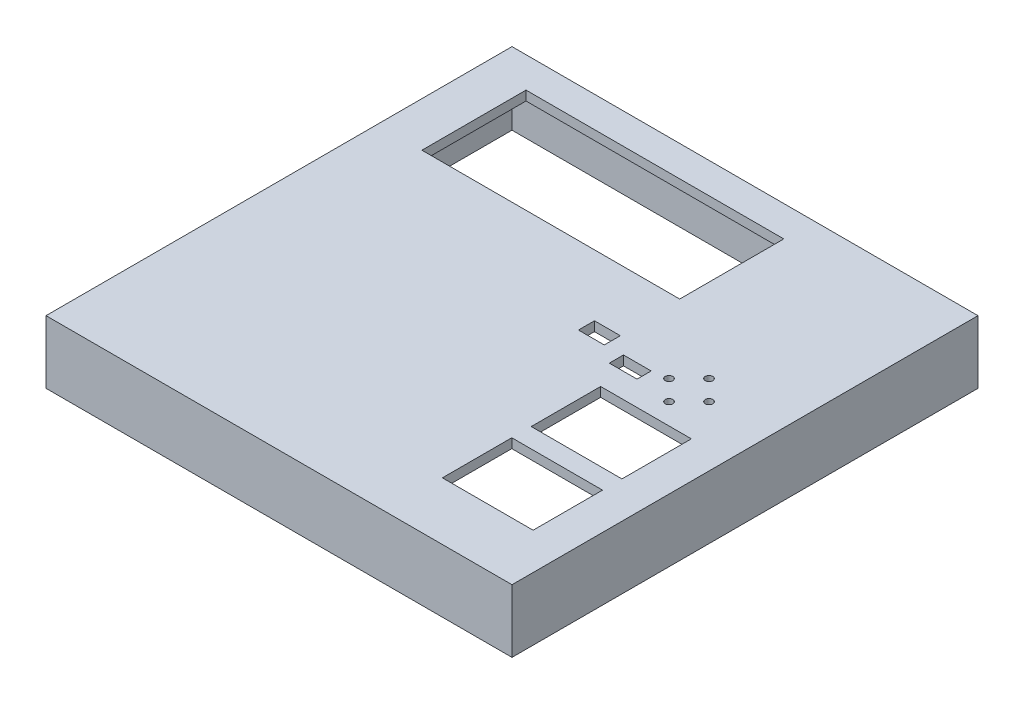
SolidWorks part; units mm, degrees
ref_plane "Front Plane" through (0, 0, 0) normal (0, 0, 1) x (1, 0, 0)
ref_plane "Top Plane" through (0, 0, 0) normal (0, 1, 0) x (1, 0, 0)
ref_plane "Right Plane" through (0, 0, 0) normal (1, 0, 0) x (0, 0, -1)
sketch "Sketch1" plane through (0, 0, 0) normal (0, 1, 0) x (1, 0, 0)
  line L1 (-39.4497, 23.4449) -> (54.5503, 23.4449)
  line L2 (-39.4497, 23.4449) -> (-39.4497, -70.5551)
  line L3 (-39.4497, -70.5551) -> (54.5503, -70.5551)
  line L4 (54.5503, 23.4449) -> (54.5503, -70.5551)
  dimension "D1" = 94
  dimension "D2" = 94
extrude "Boss-Extrude1" add sketch "Sketch1" along normal blind 12.7
sketch "Sketch2" plane through (0, 12.7, 0) normal (0, 1, 0) x (1, 0, 0)
  line L1 (-30.4389, 17.2618) -> (21.5611, 17.2618)
  line L2 (-30.4389, 17.2618) -> (-30.4389, -3.7382)
  line L3 (-30.4389, -3.7382) -> (21.5611, -3.7382)
  line L4 (21.5611, 17.2618) -> (21.5611, -3.7382)
  line L5 (16.7611, -16.1312) -> (21.9778, -16.1312)
  line L6 (-37.6389, 21.9688) -> (52.1611, 21.9688)
  line L7 (-37.6389, 21.9688) -> (-37.6389, -68.4562)
  line L8 (-37.6389, -68.4562) -> (52.1611, -68.4562)
  line L9 (52.1611, 21.9688) -> (52.1611, -68.4562)
  line L10 (28.8611, -26.9865) -> (47.1611, -26.9865)
  line L11 (28.8611, -26.9865) -> (28.8611, -40.9865)
  line L12 (28.8611, -40.9865) -> (47.1611, -40.9865)
  line L13 (47.1611, -26.9865) -> (47.1611, -40.9865)
  line L14 (28.8611, -44.9062) -> (47.1611, -44.9062)
  line L15 (28.8611, -44.9062) -> (28.8611, -58.9062)
  line L16 (28.8611, -58.9062) -> (47.1611, -58.9062)
  line L17 (47.1611, -44.9062) -> (47.1611, -58.9062)
  line L18 (16.7611, -16.1312) -> (16.7611, -19.368)
  line L19 (16.7611, -19.368) -> (21.9778, -19.368)
  line L20 (21.9778, -16.1312) -> (21.9778, -19.368)
  line L21 (25.6611, -19.1792) -> (31.2504, -19.1792)
  line L22 (25.6611, -19.1792) -> (25.6611, -22.0359)
  line L23 (25.6611, -22.0359) -> (31.2504, -22.0359)
  line L24 (31.2504, -19.1792) -> (31.2504, -22.0359)
  circle A0 centre (38.4111, -18.7062) radius 6.05
  circle A7 centre (38.4111, -14.6721) radius 0.762
  circle A8 centre (34.377, -18.7062) radius 0.762
  circle A9 centre (38.4111, -22.7403) radius 0.762
  circle A10 centre (42.4453, -18.7062) radius 0.762
  dimension "D15" = 12.1
  dimension "D18" = 1.524
  dimension "D19" = 1.524
  dimension "D20" = 1.524
  dimension "D21" = 1.524
  dimension "D1" = 21
  dimension "D2" = 52
  dimension "D3" = 7.2
  dimension "D4" = 89.8
  dimension "D5" = 90.425
  dimension "D6" = 30.6
  dimension "D7" = 4.707
  dimension "D8" = 14
  dimension "D9" = 14
  dimension "D10" = 18.3
  dimension "D11" = 18.3
  dimension "D12" = 23.3
  dimension "D13" = 9.55
  dimension "D14" = 23.3
  dimension "D16" = 49.75
  dimension "D17" = 13.75
  dimension "D22" = 35.4
  dimension "D23" = 26.5
  dimension "D24" = 41.148
  dimension "D25" = 38.1
shell "Shell3" thickness 1.905 removed face at (7.5503, 0, 23.5551)
extrude "Cut-Extrude2" cut sketch "Sketch2" against normal blind 2.54 contours L13 L10 L11 L12 | L2 L1 L4 L3 | L15 L14 L17 L16 | L11 L10 L13 L12 region at (38.0111, 12.7, 33.9865)
extrude "Cut-Extrude4" cut sketch "Sketch2<11>" against normal blind 2.54 contours A9 | A10 | A7 | A8
sketch "Sketch2<11>" plane through (0, 12.7, 0) normal (0, 1, 0) x (1, 0, 0) same geometry as "Sketch2"
extrude "Cut-Extrude5" cut sketch "Sketch2<12>" against normal blind 2.54 contours L21 L24 L23 L22 | L5 L20 L19 L18
sketch "Sketch2<12>" plane through (0, 12.7, 0) normal (0, 1, 0) x (1, 0, 0) same geometry as "Sketch2"
sketch "Sketch4" plane through (-39.4497, 0, 0) normal (-1, 0, 0) x (0, 0, 1)
  line L0 (34.3551, 9.5652) -> (34.3551, 2.6549) construction
  line L1 (24.2295, 9.5652) -> (44.4807, 9.5652)
  line L2 (24.2295, 9.5652) -> (24.2295, 2.6549)
  line L3 (24.2295, 2.6549) -> (44.4807, 2.6549)
  line L4 (44.4807, 9.5652) -> (44.4807, 2.6549)
  line L5 (70.5551, 12.7) -> (70.5551, 0) construction
  dimension "D1" = 20.2513
  dimension "D2" = 36.2
extrude "Cut-Extrude6" cut sketch "Sketch4" against normal blind 2.54 contours L1 L4 L3 L2
